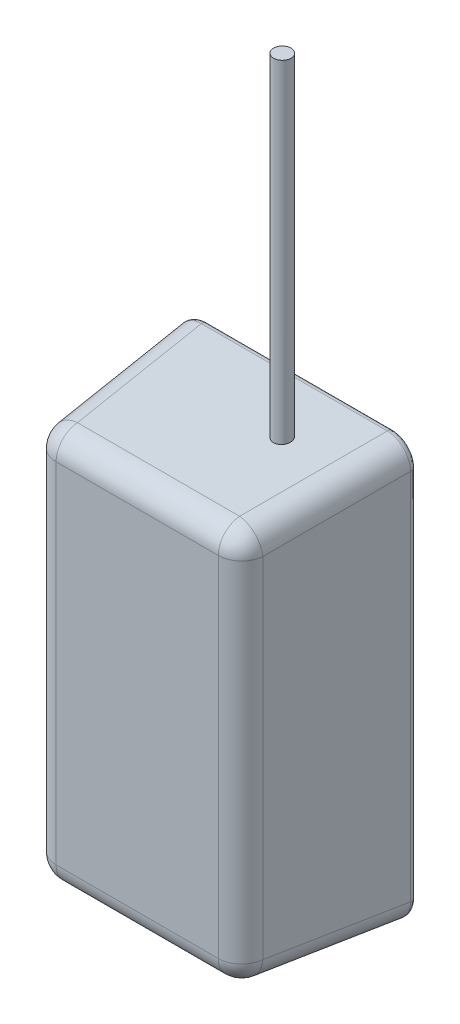
SolidWorks part; units mm, degrees
ref_plane "Front" through (0, 0, 0) normal (0, 0, 1) x (1, 0, 0)
ref_plane "Top" through (0, 0, 0) normal (0, 1, 0) x (1, 0, 0)
ref_plane "Right" through (0, 0, 0) normal (1, 0, 0) x (0, 0, -1)
sketch "Sketch1" plane through (0, 0, 0) normal (0, 0, 1) x (1, 0, 0)
  line L1 (-127, 228.6) -> (127, 228.6)
  line L2 (-127, 228.6) -> (-127, -228.6)
  line L3 (-127, -228.6) -> (127, -228.6)
  line L4 (127, 228.6) -> (127, -228.6)
  line L5 (-127, 228.6) -> (127, -228.6) construction
  line L6 (-127, -228.6) -> (127, 228.6) construction
  point P0 (0, 0)
  dimension "D1" = 254
  dimension "D2" = 457.2
extrude "Boss-Extrude1" add sketch "Sketch1" along normal blind 177.8 draft 5
fillet "Fillet1" radius 25.4 4 edges at (119.2223, -220.8223, 88.9) (-119.2223, -220.8223, 88.9) (119.2223, 220.8223, 88.9) (-119.2223, 220.8223, 88.9)
fillet "Fillet2" radius 25.4 8 edges at (-104.045, -205.645, 177.8) (-111.4445, 0, 177.8) (-104.045, 205.645, 177.8) (0, 213.0445, 177.8) (104.045, 205.645, 177.8) (111.4445, 0, 177.8) (104.045, -205.645, 177.8) (0, -213.0445, 177.8)
fillet "Fillet3" radius 6.35 8 edges at (119.6004, -221.2004, 0) (0, -228.6, 0) (-119.6004, -221.2004, 0) (-127, 0, 0) (-119.6004, 221.2004, 0) (0, 228.6, 0) (119.6004, 221.2004, 0) (127, 0, 0)
sketch "Sketch2" plane through (0, 0, 0) normal (0, 1, 0) x (1, 0, 0)
  line L0 (0, 0) -> (0, -69.85) construction
  line L1 (0, -69.85) -> (-76.2, -69.85) construction
  line L2 (0, -69.85) -> (25.4, -69.85) construction
  circle A0 centre (-76.2, -69.85) radius 3.175
  circle A1 centre (25.4, -69.85) radius 9.525
  dimension "D3" = 6.35
  dimension "D4" = 19.05
  dimension "D1" = 25.4
  dimension "D2" = 76.2
  dimension "D5" = 69.85
extrude "Boss-Extrude2" add sketch "Sketch2" against normal blind 279.4
sketch "Sketch3" plane through (0, 0, 0) normal (0, 1, 0) x (1, 0, 0)
  line L0 (0, 0) -> (0, -64.4508) construction
  line L1 (0, -64.4508) -> (44.45, -64.4508) construction
  circle A0 centre (44.45, -64.4508) radius 9.525
  dimension "D2" = 19.05
  dimension "D1" = 44.45
  dimension "D3" = 64.4508
extrude "Boss-Extrude3" add sketch "Sketch3" along normal blind 584.2
